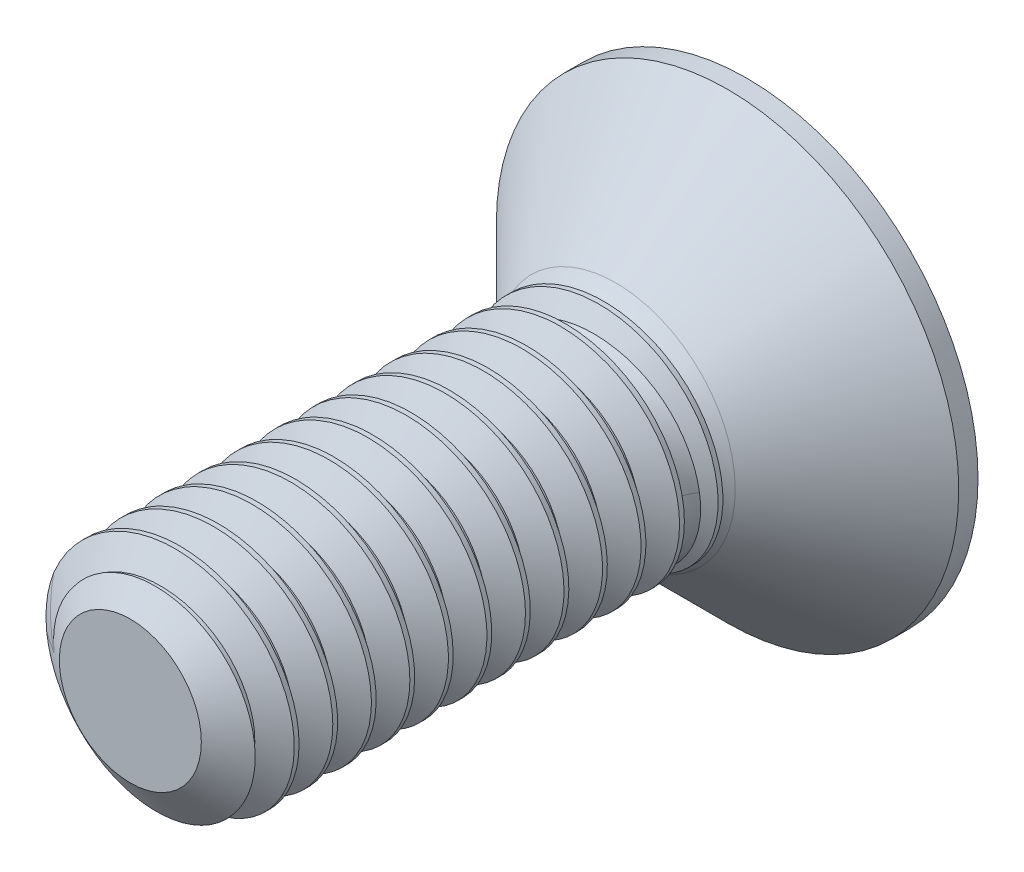
SolidWorks part; units mm, degrees
material "Alloy Steel"
ref_plane "Front Plane" through (0, 0, 0) normal (0, 0, 1) x (1, 0, 0)
ref_plane "Top Plane" through (0, 0, 0) normal (0, 1, 0) x (1, 0, 0)
ref_plane "Right Plane" through (0, 0, 0) normal (1, 0, 0) x (0, 0, -1)
sketch "Sketch1" plane through (0, 0, 0) normal (0, 0, 1) x (1, 0, 0)
  circle A0 centre (0, 0) radius 1.5
  dimension "OD" = 3
extrude "Extrude1" add sketch "Sketch1" against normal blind 8
sketch "Sketch2" plane through (0, 0, 0) normal (0, 0, 1) x (1, 0, 0)
  circle A0 centre (0, 0) radius 1.5 construction
  circle A1 centre (0, 0) radius 1.5
curve "Helix/Spiral1" pitch 0.5 height 8.5 radius 1.5 centre (0, 0, 0) axis (0, 0, -1) start towards (0, 1, 0) parameters "pitch"=0.5
sketch "Sketch3" plane through (0, 0, 0) normal (1, 0, 0) x (0, 0, -1)
  line L0 (-0.4375, 1.5) -> (-0.25, 1.1752)
  line L1 (-0.25, 1.1752) -> (-0.1875, 1.1752)
  line L2 (-0.1875, 1.1752) -> (0, 1.5)
  line L3 (-0.4375, 1.5) -> (0, 1.5)
  line L4 (-0.2188, 1.5) -> (-0.2188, 1.1752) construction
  line L5 (-0.3438, 1.3376) -> (-0.0937, 1.3376) construction
  line L6 (0, 1.5) -> (0, -1.5) construction
  dimension "D1" = 0.0625
  dimension "D2" = 0.25
  dimension "D3" = 60
sweep "Cut-Sweep1" cut profiles "Sketch3" path "Helix/Spiral1"
sketch "Sketch4" plane through (0, 0, 0) normal (1, 0, 0) x (0, 0, -1)
  line L0 (0.4053, 1.5) -> (0, 0.9212)
  line L1 (0, 0.9212) -> (0, 1.5)
  line L2 (0.4053, 1.5) -> (0, 1.5)
  line L3 (-0.4375, 1.5) -> (0, 1.5) construction
  line L4 (0, 0) -> (7.0209, 0) construction
  dimension "D1" = 55
  dimension "D2" = 0.254
revolve "Cut-Revolve1" cut sketch "Sketch4" angle 360 about L4
sketch "Sketch5" plane through (0, 0, 0) normal (1, 0, 0) x (0, 0, -1)
  line L0 (8, -1.1822) -> (8, 1.0703) construction
  line L1 (8, 1.55) -> (18.1906, 1.55)
  line L2 (8, 1.55) -> (8, 0)
  line L3 (8, 0) -> (18, 0)
  line L4 (18, 1.2198) -> (18, 0)
  line L5 (18.1906, 1.55) -> (18, 1.2198)
  line L6 (0, 0) -> (9.9695, 0) construction
  point P3 (18, 1.55)
  point P10 (18, 1.55)
  dimension "D1" = 0.3302
  dimension "Thread min" = 18
  dimension "D2" = 0.05
  dimension "D3" = 30
revolve "partially thread" [suppressed] add sketch "Sketch5" angle 360 about L6
sketch "Sketch6" plane through (0, 0, -8) normal (0, 0, -1) x (-1, 0, 0)
  circle A0 centre (0, 0) radius 3
  dimension "head dia" = 6
extrude "Extrude2" add sketch "Sketch6" against normal blind 1.7
sketch "Sketch10" plane through (0, 0, 0) normal (1, 0, 0) x (0, 0, -1)
  line L0 (7.75, -3) -> (6.3, -1.55)
  line L1 (6.3, -1.55) -> (6.3, -3)
  line L2 (7.75, -3) -> (6.3, -3)
  line L3 (0, 0) -> (6.3, 0) construction
  line L4 (6.3, 3) -> (6.3, -3) construction
  line L5 (7.75, 3) -> (6.3, 3) construction
  line L6 (6.3, 1.55) -> (6.3, 3) construction
  line L7 (7.75, 3) -> (6.3, 1.55) construction
  line L8 (6.3, 3) -> (6.3, -3) construction
  line L9 (6.3, 1.55) -> (6.3, -1.55) construction
  dimension "D1" = 45
  dimension "D2" = 0.05
revolve "Cut-Revolve2" cut sketch "Sketch10" angle 360 about L3
sketch "Sketch11" plane through (0, 0, 0) normal (1, 0, 0) x (0, 0, -1)
  line L0 (-0.25, 1.1752) -> (-0.1875, 1.1752) construction
  line L1 (7.75, 3) -> (6.3, 1.55) construction
  line L2 (5.3953, 1.1752) -> (5.3953, 0)
  line L3 (5.3953, 0) -> (6.3, 0)
  line L4 (6.3, 1.55) -> (6.3, 0)
  line L5 (0, 0) -> (6.3, 0) construction
  arc A0 (6.3, 1.55) -> (5.3953, 1.1752) centre (5.3953, 2.4547) cw
revolve "Revolve1" add sketch "Sketch11" angle 360 about L3
sketch "Sketch7" plane through (0, 0, -8) normal (0, 0, 1) x (1, 0, 0)
  line L1 (0, 1.1547) -> (-1, 0.5774)
  line L2 (-1, 0.5774) -> (-1, -0.5774)
  line L3 (-1, -0.5774) -> (0, -1.1547)
  line L4 (0, -1.1547) -> (1, -0.5774)
  line L5 (1, -0.5774) -> (1, 0.5774)
  line L6 (1, 0.5774) -> (0, 1.1547)
  circle A0 centre (0, 0) radius 1 construction
  dimension "hex dia" = 2
extrude "Cut-Extrude1" cut sketch "Sketch7" along normal blind 1.5
sketch "Sketch8" plane through (0, 0, -8) normal (0, 0, 1) x (1, 0, 0)
  circle A0 centre (0, 0) radius 1.1547
extrude "Cut-Extrude2" cut sketch "Sketch8" along normal through all draft 45
sketch "Sketch9" plane through (0, 0, 0) normal (1, 0, 0) x (0, 0, -1)
  line L0 (0, 1.5) -> (0, -1.5) construction
  line L1 (2.75, 1.5) -> (2.75, -1.5) construction
  line L2 (6.3, 1.5) -> (6.3, -1.5) construction
  line L3 (6.3, -1.55) -> (6.3, -3) construction
  dimension "D1" = 2.75
  dimension "D4" = 0.635
  dimension "D5" = 0.3302
equation "\"D3@Helix/Spiral1\" = \"screw length@Extrude1\"+\"pitch@Helix/Spiral1\""
equation "\"D1@Sketch3\" = \"pitch@Helix/Spiral1\"*.125"
equation "\"D2@Sketch3\" = \"pitch@Helix/Spiral1\"*.5"
equation "\"D1@Cut-Extrude1\" = \"hex dia@Sketch7\"*.75"
equation "\"D1@Sketch9\" = \"pitch@Helix/Spiral1\"*5.5"
equation "\"D2@Sketch10\" = \"D2@Sketch5\""
